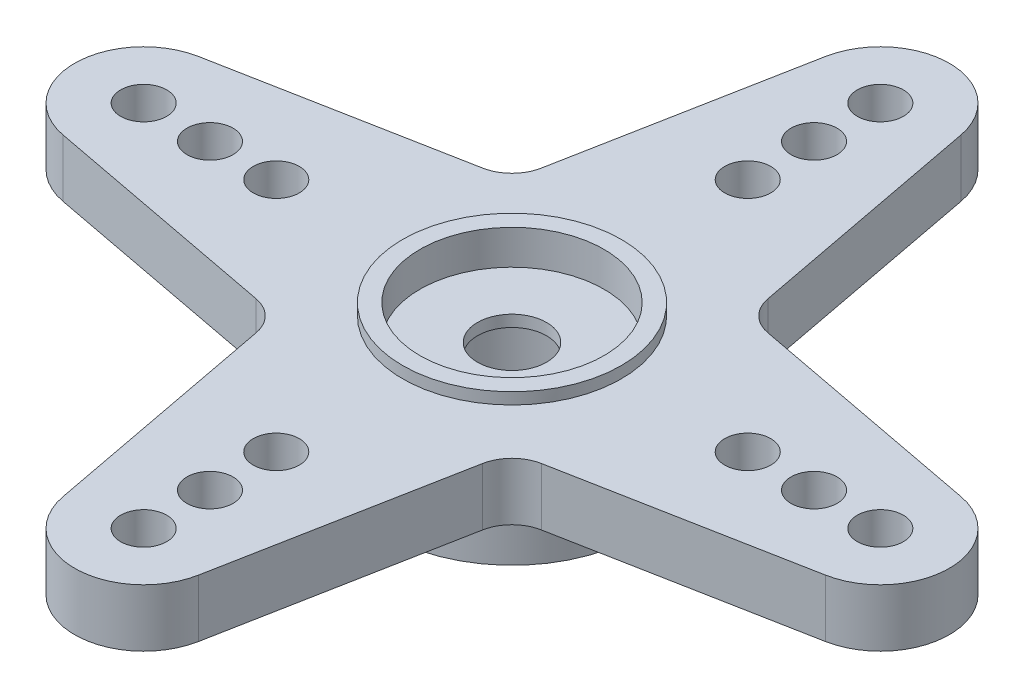
SolidWorks part; units mm, degrees
ref_plane "Front Plane" through (0, 0, 0) normal (0, 0, 1) x (1, 0, 0)
ref_plane "Top Plane" through (0, 0, 0) normal (0, 1, 0) x (1, 0, 0)
ref_plane "Right Plane" through (0, 0, 0) normal (1, 0, 0) x (0, 0, -1)
sketch "Sketch1" plane through (0, 0, 0) normal (0, 1, 0) x (1, 0, 0)
  line L0 (-1000, 0) -> (49000, 0) construction
  line L1 (0, -1000) -> (0, 49000) construction
  line L2 (-3.9044, 4.9148) -> (-2.3393, 13.1449)
  line L3 (3.9044, 4.9148) -> (2.3393, 13.1449)
  line L4 (4.9148, 3.9044) -> (13.1449, 2.3393)
  line L5 (4.9148, -3.9044) -> (13.1449, -2.3393)
  line L6 (3.9044, -4.9148) -> (2.3393, -13.1449)
  line L7 (-3.9044, -4.9148) -> (-2.3393, -13.1449)
  line L8 (-4.0659, 4.0659) -> (-4.0659, -4.0659) construction
  line L9 (-4.0659, 4.0659) -> (4.0659, 4.0659) construction
  line L10 (-4.0659, -4.0659) -> (4.0659, -4.0659) construction
  line L11 (4.0659, 4.0659) -> (4.0659, -4.0659) construction
  line L12 (-4.9148, -3.9044) -> (-13.1449, -2.3393)
  line L13 (-4.9148, 3.9044) -> (-13.1449, 2.3393)
  circle A0 centre (0, 0) radius 1.1906
  circle A1 centre (0, 0) radius 5.75 construction
  arc A2 (-2.3393, 13.1449) -> (2.3393, 13.1449) centre (0, 12.7) cw
  circle A3 centre (0, 12.7) radius 0.7937
  circle A4 centre (0, 10.414) radius 0.7937
  circle A5 centre (0, 8.128) radius 0.7937
  arc A6 (13.1449, 2.3393) -> (13.1449, -2.3393) centre (12.7, 0) cw
  circle A7 centre (12.7, 0) radius 0.7937
  circle A8 centre (10.414, 0) radius 0.7937
  circle A9 centre (8.128, 0) radius 0.7937
  arc A10 (2.3393, -13.1449) -> (-2.3393, -13.1449) centre (0, -12.7) cw
  circle A11 centre (0, -12.7) radius 0.7937
  circle A12 centre (0, -10.414) radius 0.7937
  circle A13 centre (0, -8.128) radius 0.7937
  arc A14 (-13.1449, -2.3393) -> (-13.1449, 2.3393) centre (-12.7, 0) cw
  circle A15 centre (-12.7, 0) radius 0.7937
  circle A16 centre (-10.414, 0) radius 0.7937
  circle A17 centre (-8.128, 0) radius 0.7937
  arc A18 (3.9044, 4.9148) -> (4.9148, 3.9044) centre (5.1521, 5.1521) ccw
  arc A19 (-3.9044, -4.9148) -> (-4.9148, -3.9044) centre (-5.1521, -5.1521) ccw
  arc A20 (-3.9044, 4.9148) -> (-4.9148, 3.9044) centre (-5.1521, 5.1521) cw
  arc A21 (3.9044, -4.9148) -> (4.9148, -3.9044) centre (5.1521, -5.1521) cw
  dimension "D1" = 11.5
  dimension "D2" = 2.3813
  dimension "D3" = 2.3813
  dimension "D5" = 1.5875
  dimension "D8" = 1.27
  dimension "D9" = 1.27
  dimension "D10" = 1.27
  dimension "D11" = 1.27
  dimension "D4" = 12.7
  dimension "D6" = 3
  dimension "D7" = 4
extrude "Boss-Extrude1" add sketch "Sketch1" along normal blind 1.9844
sketch "Sketch2" plane through (0, 1.9844, 0) normal (0, 1, 0) x (1, 0, 0)
  circle A0 centre (0, 0) radius 3.175
  dimension "D1" = 6.35
extrude "Cut-Extrude1" cut sketch "Sketch2" against normal blind 0.7937
sketch "Sketch3" plane through (0, 0, 0) normal (0, -1, 0) x (1, 0, 0)
  circle A0 centre (0, 0) radius 4.3656
  dimension "D1" = 8.7312
extrude "Boss-Extrude2" add sketch "Sketch3" along normal blind 2.3813
sketch "Sketch4" plane through (0, -2.3813, 0) normal (0, -1, 0) x (1, 0, 0)
  circle A0 centre (0, 0) radius 2.7781
  dimension "D1" = 5.5562
extrude "Cut-Extrude2" cut sketch "Sketch4" against normal blind 3.175
sketch "Sketch5" plane through (0, 1.9844, 0) normal (0, 1, 0) x (1, 0, 0)
  circle A0 centre (0, 0) radius 3.175
  circle A1 centre (0, 0) radius 3.7703
  dimension "D1" = 7.5406
extrude "Boss-Extrude3" add sketch "Sketch5" along normal blind 0.3969
